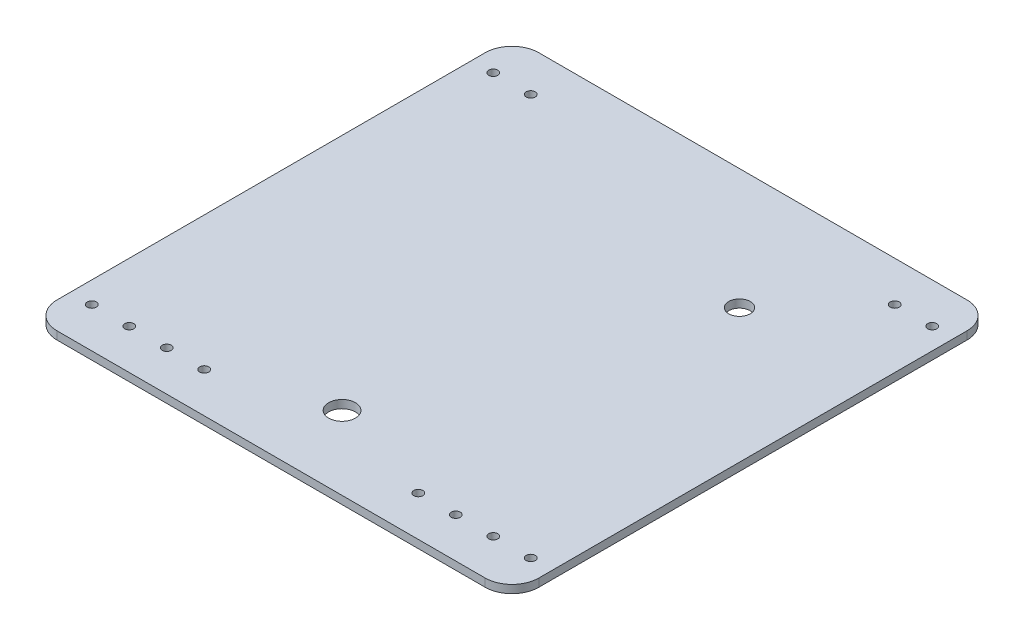
SolidWorks part; units mm, degrees
ref_plane "Front Plane" through (0, 0, 0) normal (0, 0, 1) x (1, 0, 0)
ref_plane "Top Plane" through (0, 0, 0) normal (0, 1, 0) x (1, 0, 0)
ref_plane "Right Plane" through (0, 0, 0) normal (1, 0, 0) x (0, 0, -1)
sketch "Sketch1" plane through (0, 0, 0) normal (0, 1, 0) x (1, 0, 0)
  line L1 (-90, 90) -> (90, 90)
  line L2 (-90, 90) -> (-90, -90)
  line L3 (-90, -90) -> (90, -90)
  line L4 (90, 90) -> (90, -90)
  line L5 (-90, 90) -> (90, -90) construction
  line L6 (-90, -90) -> (90, 90) construction
  point P0 (0, 0)
  dimension "D1" = 180
  dimension "D2" = 180
extrude "Boss-Extrude1" add sketch "Sketch1" along normal blind 3
fillet "Fillet1" radius 10 4 edges at (-90, 1.5, -90) (-90, 1.5, 90) (90, 1.5, -90) (90, 1.5, 90)
sketch "Sketch2" plane through (0, 3, 0) normal (0, 1, 0) x (1, 0, 0)
  circle A0 centre (-82, 75) radius 1.7
  circle A1 centre (-68, 75) radius 1.7
  circle A2 centre (68, 75) radius 1.7
  circle A3 centre (82, 75) radius 1.7
  circle A4 centre (-82, -75) radius 1.7
  circle A5 centre (-68, -75) radius 1.7
  circle A6 centre (68, -75) radius 1.7
  circle A7 centre (82, -75) radius 1.7
  circle A32 centre (-54, -75) radius 1.7
  circle A33 centre (54, -75) radius 1.7
  circle A34 centre (-40, -75) radius 1.7
  circle A35 centre (40, -75) radius 1.7
  dimension "D1" = 3.4
  dimension "D11" = 14
  dimension "D18" = 14
  dimension "D19" = 14
  dimension "D20" = 14
  dimension "D2" = 14
  dimension "D3" = 14
  dimension "D4" = 82
  dimension "D5" = 82
  dimension "D6" = 75
  dimension "D7" = 75
extrude "Cut-Extrude1" cut sketch "Sketch2" against normal up to surface (3 mm away) up to face at (0, 0, 0)
sketch "Sketch3" plane through (0, 3, 0) normal (0, 1, 0) x (1, 0, 0)
  circle A0 centre (40, 45) radius 4
  dimension "D1" = 8
  dimension "D2" = 40
  dimension "D3" = 45
extrude "Cut-Extrude2" cut sketch "Sketch3" against normal through all
sketch "Sketch4" plane through (0, 3, 0) normal (0, 1, 0) x (1, 0, 0)
  circle A0 centre (-1, -62.5) radius 5
  dimension "D2" = 10
  dimension "D3" = 1
  dimension "D1" = 62.5
extrude "Cut-Extrude3" cut sketch "Sketch4" against normal through all
